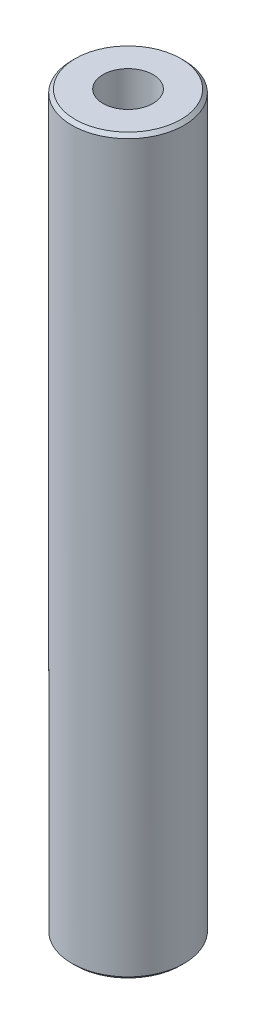
SolidWorks part; units mm, degrees
ref_plane "Front Plane" through (0, 0, 0) normal (0, 0, 1) x (1, 0, 0)
ref_plane "Top Plane" through (0, 0, 0) normal (0, 1, 0) x (1, 0, 0)
ref_plane "Right Plane" through (0, 0, 0) normal (1, 0, 0) x (0, 0, -1)
sketch "Sketch1" plane through (0, 0, 0) normal (0, 1, 0) x (1, 0, 0)
  circle A0 centre (0, 0) radius 12.5
  dimension "SHAFT_OD" = 25
extrude "Boss-Extrude1" add sketch "Sketch1" along normal blind 163.1217
sketch "Sketch2" plane through (0, 0, 0) normal (0, 1, 0) x (1, 0, 0)
  circle A0 centre (0, 0) radius 5.5744
  dimension "BORE_D" = 11.1488
extrude "Cut-Extrude1" cut sketch "Sketch2" along normal through all
chamfer "Chamfer1" distance 0.7438 angle 45 2 edges at (0, 163.1217, 12.5) (0, 0, 12.5)
